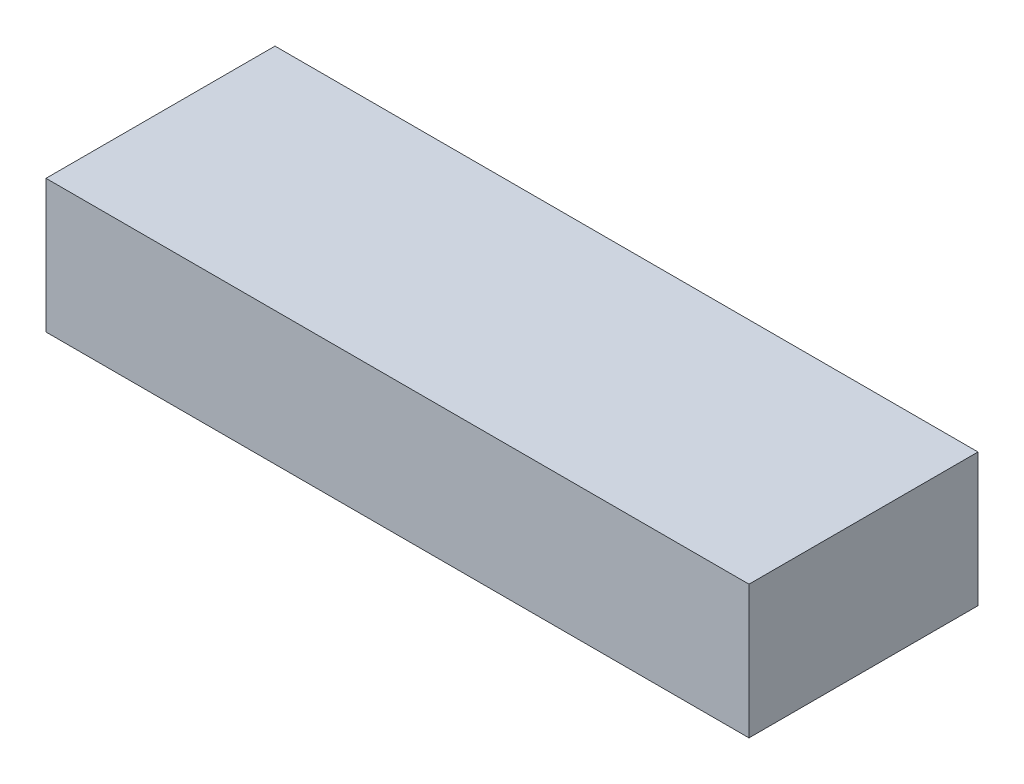
SolidWorks part; units mm, degrees
material "Rubber"
ref_plane "Front Plane" through (0, 0, 0) normal (0, 0, 1) x (1, 0, 0)
ref_plane "Top Plane" through (0, 0, 0) normal (0, 1, 0) x (1, 0, 0)
ref_plane "Right Plane" through (0, 0, 0) normal (1, 0, 0) x (0, 0, -1)
sketch "Sketch1" plane through (0, 0, 0) normal (0, 1, 0) x (1, 0, 0)
  line L1 (-66, 21.5) -> (66, 21.5)
  line L2 (-66, 21.5) -> (-66, -21.5)
  line L3 (-66, -21.5) -> (66, -21.5)
  line L4 (66, 21.5) -> (66, -21.5)
  line L5 (-66, 21.5) -> (66, -21.5) construction
  line L6 (-66, -21.5) -> (66, 21.5) construction
  point P0 (0, 0)
  dimension "D1" = 132
  dimension "D2" = 43
extrude "Boss-Extrude1" add sketch "Sketch1" along normal blind 25
